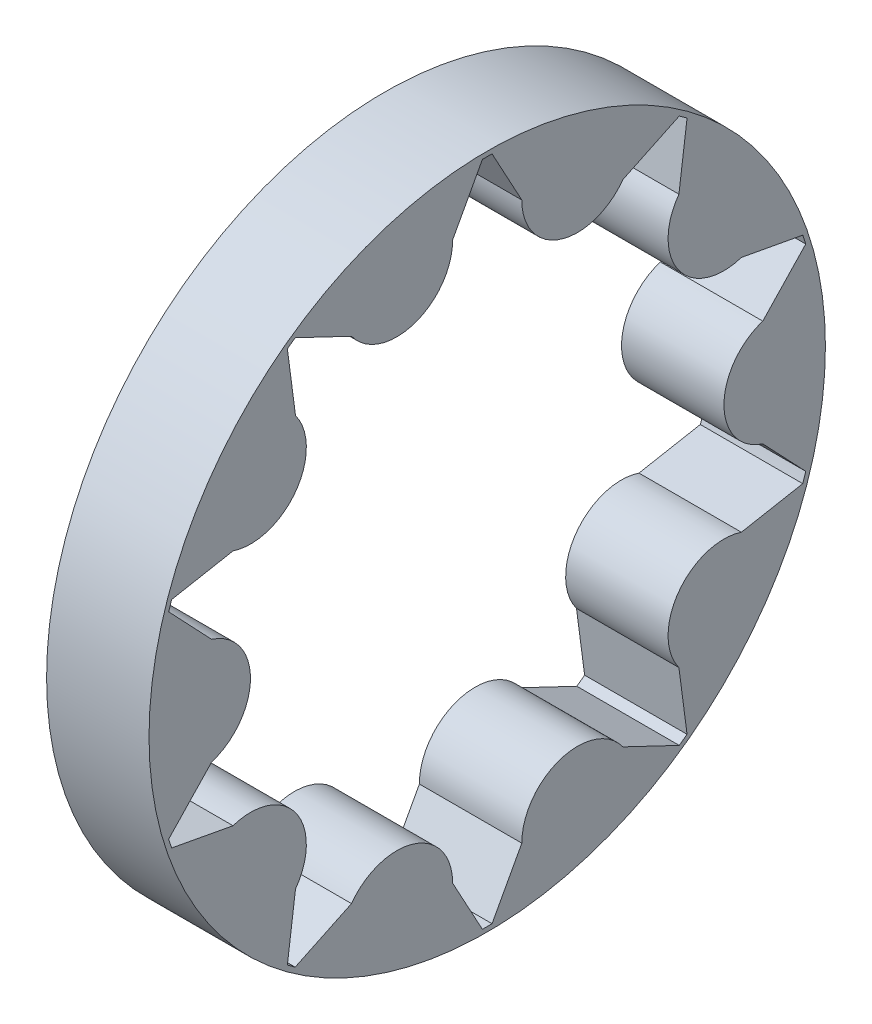
SolidWorks part; units mm, degrees
ref_plane "Front Plane" through (0, 0, 0) normal (0, 0, 1) x (1, 0, 0)
ref_plane "Top Plane" through (0, 0, 0) normal (0, 1, 0) x (1, 0, 0)
ref_plane "Right Plane" through (0, 0, 0) normal (1, 0, 0) x (0, 0, -1)
sketch "Sketch1" plane through (0, 0, 0) normal (1, 0, 0) x (0, 0, -1)
  line L0 (0, 0) -> (0, 17.25)
  line L1 (0, 0) -> (10.1393, 13.9555)
  line L4 (10.1393, 13.9555) -> (9.936, 14.101)
  line L5 (9.936, 14.101) -> (7.0217, 12.7115)
  line L6 (0, 0) -> (3.7855, 11.6504) construction
  line L7 (0.25, 17.2482) -> (1.7909, 14.4111)
  line L8 (10.1393, 13.9555) -> (10.2862, 14.1578)
  line L9 (0, 17.25) -> (0, 17.5)
  circle A0 centre (0, 0) radius 12.25
  circle A1 centre (0, 0) radius 17.25
  circle A2 centre (0, 0) radius 14.5219 construction
  arc A3 (1.7909, 14.4111) -> (7.0217, 12.7115) centre (4.6775, 14.3958) ccw
  circle A4 centre (0, 0) radius 17.5
  point P10 (10.0376, 14.0283)
  point P13 (0.125, 17.2491)
  dimension "D1" = 24.5
  dimension "D2" = 34.5
  dimension "D3" = 0.25
  dimension "D6" = 35
  dimension "D4" = 36
  dimension "D5" = 5.5
extrude "Boss-Extrude1" add sketch "Sketch1" along normal blind 5.3 contours L7 A3 L5 A1 | L8 A4 L9 A1 region at (0, 17.375, -0.1088) region at (0, 14.4205, -4.6855)
pattern_circular "CirPattern2" count 10 over 360 about axis through (5.3, 0, 0) along (-1, 0, 0) of "Boss-Extrude1" reverse direction yes
